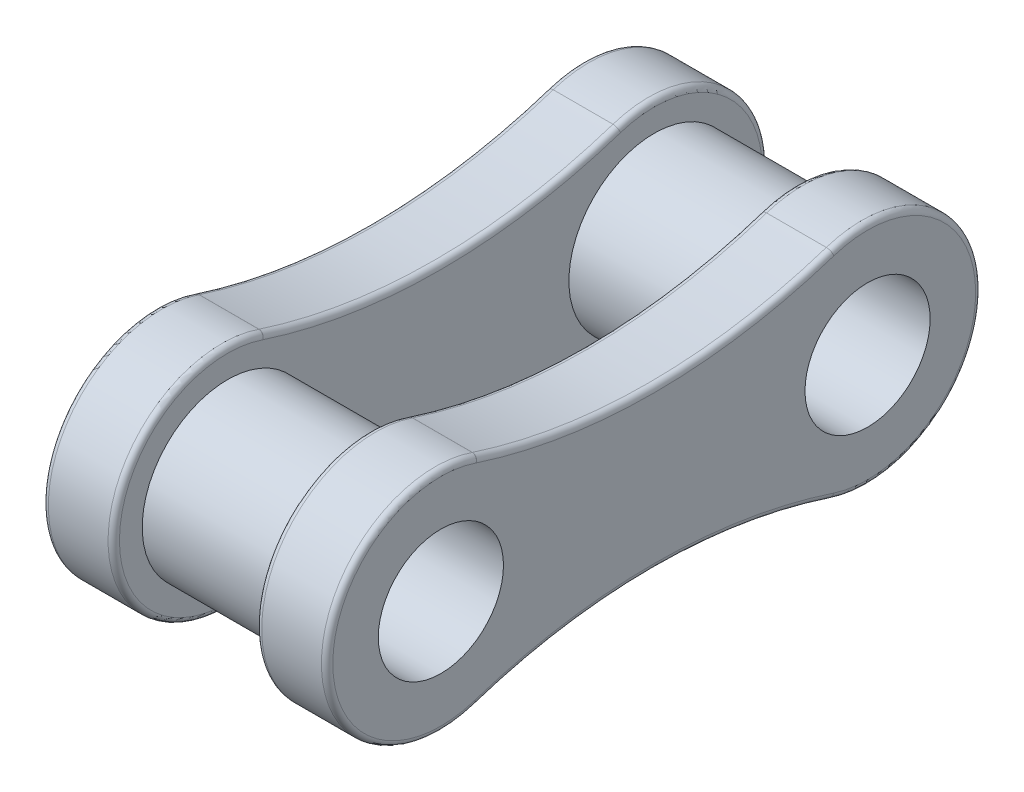
SolidWorks part; units mm, degrees
material "2018 Alloy"
ref_plane "Front Plane" through (0, 0, 0) normal (0, 0, 1) x (1, 0, 0)
ref_plane "Top Plane" through (0, 0, 0) normal (0, 1, 0) x (1, 0, 0)
ref_plane "Right Plane" through (0, 0, 0) normal (1, 0, 0) x (0, 0, -1)
sketch "Sketch2" plane through (0, 0, 0) normal (1, 0, 0) x (0, 0, -1)
  line L0 (0, 0) -> (59.047, 0) construction
  circle A0 centre (0, 0) radius 5.588
  circle A1 centre (38.1, 0) radius 5.588
  circle A2 centre (0, 0) radius 10.16
  circle A3 centre (38.1, 0) radius 10.16
  arc A4 (3.3131, 9.6046) -> (34.9247, 9.6511) centre (19.048, 57.9063) ccw
  arc A5 (3.175, -9.6512) -> (34.925, -9.6512) centre (19.05, -57.907) cw
  dimension "D2" = 11.176
  dimension "D3" = 20.32
  dimension "D4" = 50.8
  dimension "D5" = 50.8
  dimension "D1" = 38.1
sketch "Sketch3" plane through (0, 0, 0) normal (1, 0, 0) x (0, 0, -1)
  circle A0 centre (0, 0) radius 7.62
  circle A1 centre (38.1, 0) radius 7.62
  circle A2 centre (0, 0) radius 5.588 construction
  circle A3 centre (0, 0) radius 5.588
  circle A4 centre (38.1, 0) radius 5.588 construction
  circle A5 centre (38.1, 0) radius 5.588
  dimension "D1" = 15.24
  dimension "D2" = 15.24
extrude "Boss-Extrude1" add sketch "Sketch3" along normal mid plane 12.7
sketch "Sketch4" plane through (6.35, 0, 0) normal (1, 0, 0) x (0, 0, -1)
  arc A1 (34.925, -9.6512) -> (3.175, -9.6512) centre (19.05, -57.907) ccw construction
  circle A2 centre (38.1, 0) radius 10.16
  arc A3 (34.925, -9.6512) -> (34.9247, 9.6511) centre (38.1, 0) ccw
  circle A4 centre (0, 0) radius 10.16
  arc A5 (3.3131, 9.6046) -> (3.175, -9.6512) centre (0, 0) ccw
  circle A6 centre (38.1, 0) radius 5.588
  circle A7 centre (38.1, 0) radius 5.588
  circle A8 centre (0, 0) radius 5.588
  circle A9 centre (0, 0) radius 5.588
  arc A10 (3.3131, 9.6046) -> (34.9247, 9.6511) centre (19.048, 57.9063) ccw construction
  arc A11 (34.925, -9.6512) -> (3.175, -9.6512) centre (19.05, -57.907) ccw
  arc A12 (3.3131, 9.6046) -> (34.9247, 9.6511) centre (19.048, 57.9063) ccw
  dimension "D1" = 0
  dimension "D2" = 0
  dimension "D3" = 0
  dimension "D4" = 0
extrude "Boss-Extrude2" add sketch "Sketch4" along normal blind 6.35
sketch "Sketch5" plane through (-6.35, 0, 0) normal (-1, 0, 0) x (0, 0, 1)
  arc A0 (-3.175, -9.6512) -> (-34.925, -9.6512) centre (-19.05, -57.907) ccw construction
  circle A1 centre (-38.1, 0) radius 10.16
  arc A2 (-34.9247, 9.6511) -> (-34.925, -9.6512) centre (-38.1, 0) ccw
  circle A3 centre (0, 0) radius 10.16
  arc A4 (-3.175, -9.6512) -> (-3.3131, 9.6046) centre (0, 0) ccw
  circle A5 centre (-38.1, 0) radius 5.588
  circle A6 centre (-38.1, 0) radius 5.588
  circle A7 centre (0, 0) radius 5.588
  circle A8 centre (0, 0) radius 5.588
  arc A9 (-34.9247, 9.6511) -> (-3.3131, 9.6046) centre (-19.048, 57.9063) ccw construction
  arc A10 (-3.175, -9.6512) -> (-34.925, -9.6512) centre (-19.05, -57.907) ccw
  arc A11 (-34.9247, 9.6511) -> (-3.3131, 9.6046) centre (-19.048, 57.9063) ccw
  dimension "D1" = 0
  dimension "D2" = 0
  dimension "D3" = 0
  dimension "D4" = 0
extrude "Boss-Extrude3" add sketch "Sketch5" along normal blind 6.35
fillet "Fillet1" radius 0.508 18 edges at (-12.7, 0.0729, 10.1597) (-12.7, -7.107, -19.05) (-12.7, 0.0002, -48.26) (-6.35, 0.0729, 10.1597) (-6.35, -7.107, -19.05) (-6.35, 0.0002, -48.26) (12.7, 0.0729, 10.1597) (12.7, -7.107, -19.05) (12.7, 0.0002, -48.26) (6.35, 0.0729, 10.1597) (6.35, -7.107, -19.05) (6.35, 0.0002, -48.26) (-9.525, 9.6046, -3.3131) (-12.7, 7.1064, -19.1226) (-6.35, 7.1064, -19.1226) (12.7, 7.1064, -19.1226) (9.525, 9.6046, -3.3131) (6.35, 7.1064, -19.1226)
ref_plane "Plane1" through (0, 0, 0) normal (1, 0, 0) x (0, 0, -1)
sketch "Sketch6" plane through (0, 0, 0) normal (1, 0, 0) x (0, 0, -1)
  circle A0 centre (38.1, 0) radius 5.588 construction
  circle A1 centre (0, 0) radius 5.588 construction
  circle A2 centre (38.1, 0) radius 5.588
  circle A3 centre (0, 0) radius 5.588
